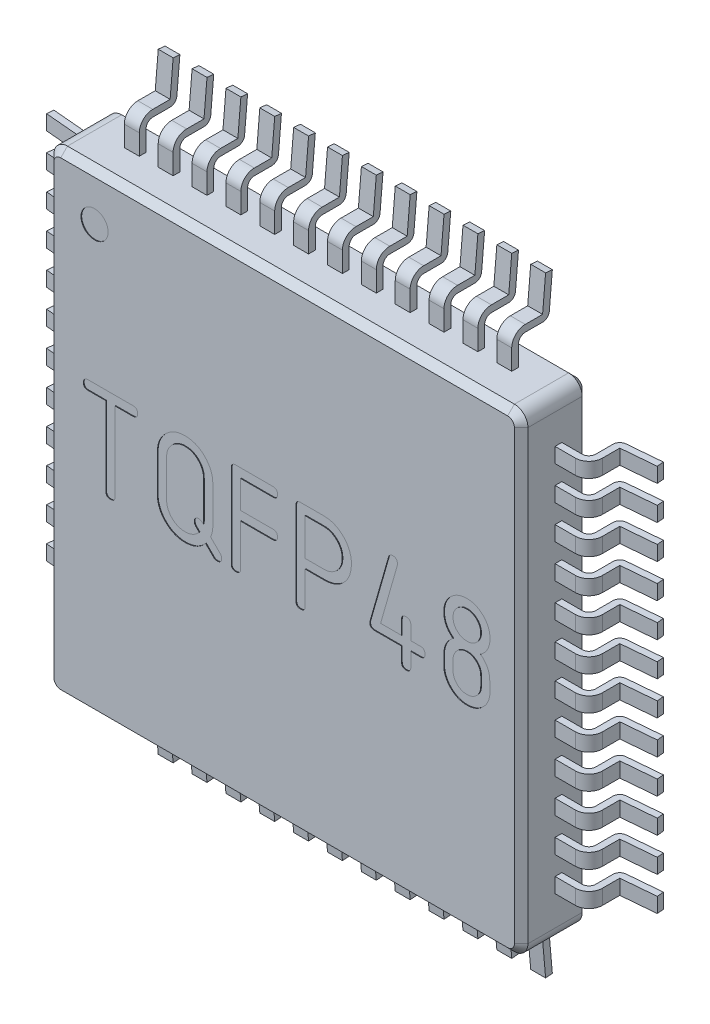
SolidWorks part; units mm, degrees
ref_plane "Спереди" through (0, 0, 0) normal (0, 0, 1) x (1, 0, 0)
ref_plane "Сверху" through (0, 0, 0) normal (0, 1, 0) x (1, 0, 0)
ref_plane "Справа" through (0, 0, 0) normal (1, 0, 0) x (0, 0, -1)
ref_axis "Ось1" through (0, 0, -0.055) along (0, 0, 1)
sketch "Эскиз1" plane through (0, 0, 0) normal (0, 0, 1) x (1, 0, 0)
  line L0 (0, 0) -> (-4.5, 0) construction
  line L1 (-3.5, -3.5) -> (3.5, -3.5)
  line L2 (-3.5, -3.5) -> (-3.5, 3.5)
  line L3 (-3.5, 3.5) -> (3.5, 3.5)
  line L4 (3.5, -3.5) -> (3.5, 3.5)
  line L5 (-3.5, -3.5) -> (3.5, 3.5) construction
  line L6 (-3.5, 3.5) -> (3.5, -3.5) construction
  line L7 (-4.5, -4.5) -> (4.5, -4.5)
  line L8 (-4.5, -4.5) -> (-4.5, 4.5)
  line L9 (-4.5, 4.5) -> (4.5, 4.5)
  line L10 (4.5, -4.5) -> (4.5, 4.5)
  line L11 (-4.5, -4.5) -> (4.5, 4.5) construction
  line L12 (-4.5, 4.5) -> (4.5, -4.5) construction
  point P0 (0, 0)
  point P6 (0, 0)
  point P13 (-3.5, 0.75)
  point P14 (-3.5, 1.25)
  point P15 (-3.5, 1.75)
  point P16 (-3.5, 2.25)
  point P17 (-3.5, -2.25)
  point P18 (-3.5, -1.75)
  point P19 (-3.5, -1.25)
  point P20 (-3.5, -0.75)
  point P21 (-3.5, 0.25)
  point P22 (-3.5, 2.75)
  point P23 (-3.5, -2.75)
  point P24 (-3.5, -0.25)
ref_plane "Плоскость1" through (0, 0, 0.1) normal (0, 0, 1) x (1, 0, 0)
ref_plane "Плоскость2" through (0, 2.75, 0) normal (0, 1, 0) x (-1, 0, 0)
sketch "Эскиз2" plane through (0, 0, 0.1) normal (0, 0, 1) x (1, 0, 0)
  line L0 (-3.5, 3.5) -> (3.5, 3.5) construction
  line L1 (-3.5, -3.5) -> (-3.5, 3.5) construction
  line L2 (-3.5, -3.5) -> (3.5, -3.5) construction
  line L3 (3.5, -3.5) -> (3.5, 3.5) construction
  line L4 (-3.3, 3.5) -> (3.3, 3.5)
  line L5 (-3.5, -3.3) -> (-3.5, 3.3)
  line L6 (-3.3, -3.5) -> (3.3, -3.5)
  line L7 (3.5, -3.3) -> (3.5, 3.3)
  arc A0 (-3.5, -3.3) -> (-3.3, -3.5) centre (-3.3, -3.3) ccw
  arc A1 (3.3, -3.5) -> (3.5, -3.3) centre (3.3, -3.3) ccw
  arc A2 (3.3, 3.5) -> (3.5, 3.3) centre (3.3, 3.3) cw
  arc A3 (-3.3, 3.5) -> (-3.5, 3.3) centre (-3.3, 3.3) ccw
  dimension "D1" = 0.2
extrude "Бобышка-Вытянуть1" add sketch "Эскиз2" along normal blind 1
chamfer "Фаска1" distance 0.1 angle 45 16 edges at (0, 3.5, 0.1) (-3.4414, 3.4414, 0.1) (3.4414, 3.4414, 0.1) (-3.5, 0, 0.1) (3.5, 0, 0.1) (-3.4414, -3.4414, 0.1) (3.4414, -3.4414, 0.1) (0, -3.5, 0.1) (0, 3.5, 1.1) (-3.4414, 3.4414, 1.1) (3.4414, 3.4414, 1.1) (-3.5, 0, 1.1) (3.5, 0, 1.1) (-3.4414, -3.4414, 1.1) (3.4414, -3.4414, 1.1) (0, -3.5, 1.1)
sketch "Эскиз3" plane through (0, 2.75, 0) normal (0, 1, 0) x (-1, 0, 0)
  line L0 (3.5, 0.5) -> (3.8, 0.5)
  line L1 (3.9, 0.4) -> (3.9, 0.1441)
  line L2 (3.9913, 0.0445) -> (4.5, 0)
  line L3 (55, 0) -> (-55, 0) construction
  line L4 (3.5, 0.6) -> (3.8, 0.6)
  line L5 (4, 0.4) -> (4, 0.1441)
  line L6 (4, 0.1441) -> (4.5087, 0.0996)
  line L7 (3.5, 0.5) -> (3.5, 0.6)
  line L8 (4.5, 0) -> (4.5087, 0.0996)
  arc A0 (3.9, 0.1441) -> (3.9913, 0.0445) centre (4, 0.1441) ccw
  arc A1 (3.8, 0.5) -> (3.9, 0.4) centre (3.8, 0.4) cw
  arc A2 (3.8, 0.6) -> (4, 0.4) centre (3.8, 0.4) cw
  arc A3 (4, 0.1441) -> (4, 0.1441) centre (4, 0.1441) ccw
  dimension "D1" = 0.1
  dimension "D2" = 0.6
  dimension "D3" = 5
  dimension "D4" = 0.5
  dimension "D5" = 0.1
extrude "Бобышка-Вытянуть2" add sketch "Эскиз3" along normal blind 0.11 and the other way blind 0.11
pattern_linear "Линейный массив1" count 12 spacing 0.5 along (0, -1, 0) of "Бобышка-Вытянуть2"
pattern_circular "Круговой массив1" count 4 over 360 about axis through (0, 0, -0.055) along (0, 0, 1) of "Бобышка-Вытянуть2", "Линейный массив1"
sketch "Эскиз4" plane through (0, 0, 1.1) normal (0, 0, 1) x (1, 0, 0)
  circle A0 centre (-2.8, 2.8) radius 0.2
  text T0 "TQFP48" font "@Adobe Fan Heiti Std B" height in points 6
  dimension "D1" = 0.4
  dimension "D2" = 3.1
  dimension "D3" = 0.6
extrude "Вырез-Вытянуть1" cut sketch "Эскиз4" against normal blind 0.01
